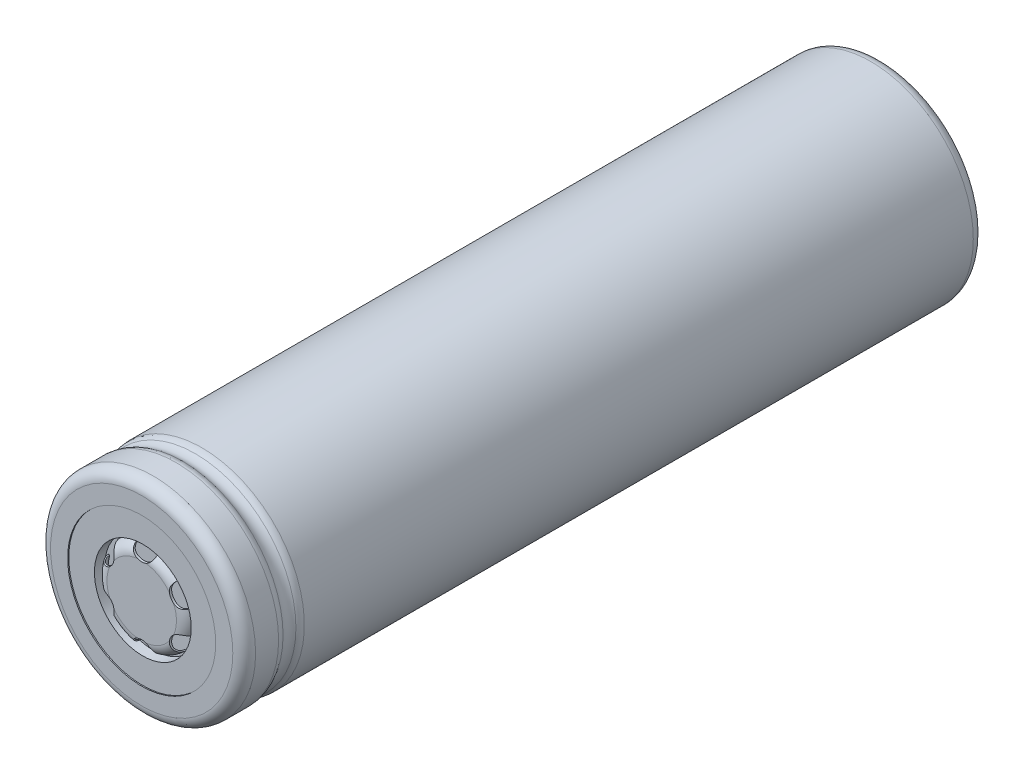
SolidWorks part; units mm, degrees
ref_plane "Спереди" through (0, 0, 0) normal (0, 0, 1) x (1, 0, 0)
ref_plane "Сверху" through (0, 0, 0) normal (0, 1, 0) x (1, 0, 0)
ref_plane "Справа" through (0, 0, 0) normal (1, 0, 0) x (0, 0, -1)
sketch "Эскиз1" plane through (0, 0, 0) normal (0, 0, 1) x (1, 0, 0)
  circle A0 centre (0, 0) radius 9
  dimension "D1" = 18
extrude "Бобышка-Вытянуть1" add sketch "Эскиз1" along normal blind 65
sketch "Эскиз2" plane through (0, 0, 65) normal (0, 0, 1) x (1, 0, 0)
  circle A0 centre (0, 0) radius 4.25
  circle A1 centre (0, 0) radius 4.05
  dimension "D1" = 8.5
  dimension "D2" = 8.1
extrude "Вырез-Вытянуть1" cut sketch "Эскиз2" against normal blind 1
sketch "Эскиз3" plane through (0, 0, 65) normal (0, 0, 1) x (1, 0, 0)
  circle A0 centre (0, 0) radius 6.5
  circle A1 centre (0, 0) radius 4.25 construction
  circle A2 centre (0, 0) radius 4.25
  dimension "D1" = 13
extrude "Вырез-Вытянуть2" cut sketch "Эскиз3" against normal blind 0.1
fillet "Скругление1" radius 1 2 edges at (9, 0, 0) (9, 0, 65)
sketch "Эскиз4" plane through (0, 0, 0) normal (0, 0, -1) x (-1, 0, 0)
  circle A0 centre (0, 0) radius 6.5
  dimension "D1" = 13
extrude "Вырез-Вытянуть3" cut sketch "Эскиз4" against normal blind 0.1
fillet "Скругление2" radius 1 1 edges at (4.05, 0, 65)
sketch "Эскиз5" plane through (0, 0, 65) normal (0, 0, 1) x (1, 0, 0)
  line L0 (0, 0) -> (0, 4.25) construction
  circle A0 centre (0, 0) radius 4.25 construction
  arc A1 (-0.9994, 3.9248) -> (0.9994, 3.9248) centre (0, 3.9601) ccw
  circle A2 centre (0, 0) radius 4.05 construction
  arc A4 (2.8993, 2.8279) -> (3.8986, 1.0969) centre (3.4296, 1.9801) ccw
  arc A5 (3.8986, -1.0969) -> (2.8993, -2.8279) centre (3.4296, -1.9801) ccw
  arc A6 (0.9994, -3.9248) -> (-0.9994, -3.9248) centre (0, -3.9601) ccw
  arc A7 (-2.8993, -2.8279) -> (-3.8986, -1.0969) centre (-3.4296, -1.9801) ccw
  arc A8 (-3.8986, 1.0969) -> (-2.8993, 2.8279) centre (-3.4296, 1.9801) ccw
  arc A9 (-2.8993, 2.8279) -> (-3.8986, 1.0969) centre (0, 0) ccw
  arc A10 (0.9994, 3.9248) -> (-0.9994, 3.9248) centre (0, 0) ccw
  arc A11 (3.8986, 1.0969) -> (2.8993, 2.8279) centre (0, 0) ccw
  arc A12 (2.8993, -2.8279) -> (3.8986, -1.0969) centre (0, 0) ccw
  arc A13 (-0.9994, -3.9248) -> (0.9994, -3.9248) centre (0, 0) ccw
  arc A14 (-3.8986, -1.0969) -> (-2.8993, -2.8279) centre (0, 0) ccw
  point P28 (0, 0)
  dimension "D1" = 1
  dimension "D2" = 1.9987
  dimension "D3" = 6
extrude "Вырез-Вытянуть4" cut sketch "Эскиз5" against normal blind 1
sketch "Эскиз6" plane through (0, 0, 0) normal (0, 1, 0) x (1, 0, 0)
  line L2 (0.3629, -65) -> (2.4411, -65) construction
  line L3 (-2.4411, -65) -> (-0.3629, -65) construction
  line L4 (0.3629, -65) -> (2.4411, -65)
  line L5 (-2.4411, -65) -> (-0.3629, -65)
  line L8 (-3.2, -64.8) -> (0, -64.8)
  line L9 (-2.4411, -64.8) -> (-0.3629, -64.8) construction
  line L10 (0, 0) -> (0, -67.0085) construction
  line L11 (-3.95, -64.05) -> (0, -64.05)
  line L12 (0, -64.05) -> (0, -64.8)
  arc A0 (-3.2, -64.8) -> (-3.95, -64.05) centre (-3.2, -64.05) cw
  dimension "D3" = 3.2
  dimension "D2" = 0.75
  dimension "D1" = 0.2
revolve "Вырез-Повернуть1" cut sketch "Эскиз6" angle 360 about L10 region at (-1.8982, 0, 64.4162)
sketch "Эскиз7" plane through (0, 0, 64.05) normal (0, 0, 1) x (1, 0, 0)
  arc A12 (2.8161, 2.7698) -> (3.8068, 1.0539) centre (3.4296, 1.9801) ccw
  arc A13 (2.8161, 2.7698) -> (0.9907, 3.8238) centre (0, 0) ccw
  arc A14 (-0.9907, 3.8238) -> (0.9907, 3.8238) centre (0, 3.9601) ccw
  arc A15 (-0.9907, 3.8238) -> (-2.8161, 2.7698) centre (0, 0) ccw
  arc A16 (-3.8068, 1.0539) -> (-2.8161, 2.7698) centre (-3.4296, 1.9801) ccw
  arc A17 (-3.8068, 1.0539) -> (-3.8068, -1.0539) centre (0, 0) ccw
  arc A18 (-2.8161, -2.7698) -> (-3.8068, -1.0539) centre (-3.4296, -1.9801) ccw
  arc A19 (-2.8161, -2.7698) -> (-0.9907, -3.8238) centre (0, 0) ccw
  arc A20 (0.9907, -3.8238) -> (-0.9907, -3.8238) centre (0, -3.9601) ccw
  arc A21 (0.9907, -3.8238) -> (2.8161, -2.7698) centre (0, 0) ccw
  arc A22 (3.8068, -1.0539) -> (2.8161, -2.7698) centre (3.4296, -1.9801) ccw
  arc A23 (3.8068, -1.0539) -> (3.8068, 1.0539) centre (0, 0) ccw
  arc A24 (2.8161, 2.7698) -> (3.8068, 1.0539) centre (3.4296, 1.9801) ccw
  arc A25 (2.8161, 2.7698) -> (0.9907, 3.8238) centre (0, 0) ccw
  arc A26 (-0.9907, 3.8238) -> (0.9907, 3.8238) centre (0, 3.9601) ccw
  arc A27 (-0.9907, 3.8238) -> (-2.8161, 2.7698) centre (0, 0) ccw
  arc A28 (-3.8068, 1.0539) -> (-2.8161, 2.7698) centre (-3.4296, 1.9801) ccw
  arc A29 (-3.8068, 1.0539) -> (-3.8068, -1.0539) centre (0, 0) ccw
  arc A30 (-2.8161, -2.7698) -> (-3.8068, -1.0539) centre (-3.4296, -1.9801) ccw
  arc A31 (-2.8161, -2.7698) -> (-0.9907, -3.8238) centre (0, 0) ccw
  arc A32 (0.9907, -3.8238) -> (-0.9907, -3.8238) centre (0, -3.9601) ccw
  arc A33 (0.9907, -3.8238) -> (2.8161, -2.7698) centre (0, 0) ccw
  arc A34 (3.8068, -1.0539) -> (2.8161, -2.7698) centre (3.4296, -1.9801) ccw
  arc A35 (3.8068, -1.0539) -> (3.8068, 1.0539) centre (0, 0) ccw
  dimension "D1" = 0
extrude "Вырез-Вытянуть5" cut sketch "Эскиз7" against normal up to surface (0.05 mm away) up to face at (0, 0, 64)
sketch "Эскиз8" plane through (0, 0, 0) normal (0, 1, 0) x (1, 0, 0)
  line L0 (9.5867, -61.848) -> (9.5867, -59.852)
  line L1 (-8, -65) -> (8, -65) construction
  line L2 (0, 0) -> (0, -84.4174) construction
  arc A0 (9.5867, -61.848) -> (9.5867, -59.852) centre (9.65, -60.85) cw
  dimension "D2" = 1
  dimension "D1" = 4.15
  dimension "D3" = 9.65
  dimension "D4" = 1.996
revolve "Вырез-Повернуть2" cut sketch "Эскиз8" angle 360 about L2
fillet "Скругление3" radius 1 2 edges at (-9, 0, 61.6099) (9, 0, 60.0901)
